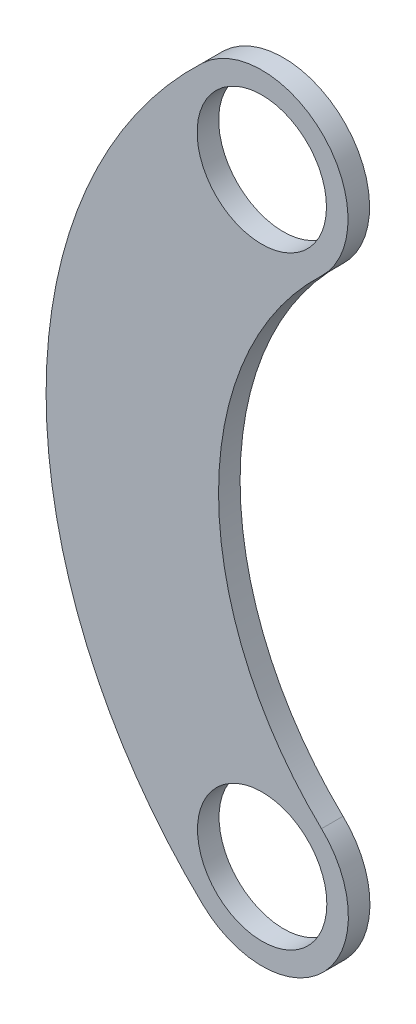
SolidWorks part; units mm, degrees
ref_plane "Front Plane" through (0, 0, 0) normal (0, 0, 1) x (1, 0, 0)
ref_plane "Top Plane" through (0, 0, 0) normal (0, 1, 0) x (1, 0, 0)
ref_plane "Right Plane" through (0, 0, 0) normal (1, 0, 0) x (0, 0, -1)
sketch "Esquisse1" plane through (0, 0, 0) normal (0, 0, 1) x (1, 0, 0)
  arc A0 (-54.4842, -22.2361) -> (-54.4671, -50.2361) centre (-41.1907, -36.228) ccw construction
  arc A1 (-57.2393, -19.3363) -> (-57.2187, -53.1394) centre (-41.1907, -36.228) ccw
  arc A2 (-51.729, -25.136) -> (-51.7155, -47.3329) centre (-41.1907, -36.228) ccw
  arc A3 (-51.729, -25.136) -> (-57.2393, -19.3363) centre (-54.4842, -22.2361) ccw
  arc A4 (-57.2187, -53.1394) -> (-51.7155, -47.3329) centre (-54.4671, -50.2361) ccw
  circle A5 centre (-54.4842, -22.2361) radius 3
  circle A6 centre (-54.4671, -50.2361) radius 3
  point P3 (-60.4907, -36.2398)
  dimension "D1" = 8
  dimension "D2" = 6
  dimension "D3" = 15.3
base flange "Tôle de base pliée1" sketch "Esquisse1" thickness 1 reverse thickness direction no parameters "D1"=0.7366
sketch "Bend-Lines1" [suppressed] plane through (0, 0, 0) normal (0, 1, 0) x (1, 0, 0)
sketch "Bounding-Box1" [suppressed] plane through (0, 0, 0) normal (0, 1, 0) x (1, 0, 0)
sheet metal parameters "Sheet-Metal1" thickness 1 parameters "D1"=0.7366
flat pattern "Flat-Pattern1" [suppressed]
sketch "Bend-Lines2" plane through (0, 0, 0) normal (0, 1, 0) x (1, 0, 0)
sketch3d "Bounding-Box2" [suppressed]
  line L0 (-2.9878, 10.9981, 0) -> (-2.9655, -25.0016, 0) construction
  line L1 (-16.7979, 10.9896, 0) -> (-16.7756, -25.0102, 0) construction
  line L2 (-2.9878, 10.9981, 0) -> (-16.7979, 10.9896, 0) construction
  line L3 (-2.9655, -25.0016, 0) -> (-16.7756, -25.0102, 0) construction
